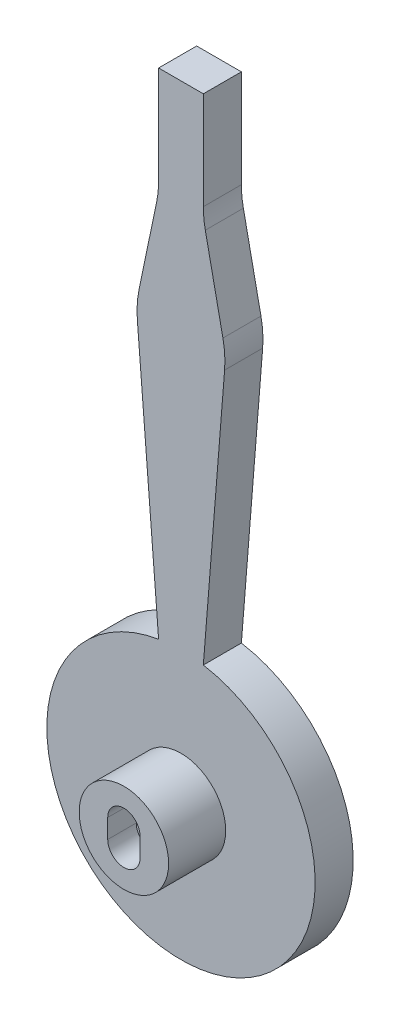
SolidWorks part; units mm, degrees
ref_plane "Front Plane" through (0, 0, 0) normal (0, 0, 1) x (1, 0, 0)
ref_plane "Top Plane" through (0, 0, 0) normal (0, 1, 0) x (1, 0, 0)
ref_plane "Right Plane" through (0, 0, 0) normal (1, 0, 0) x (0, 0, -1)
sketch "Sketch1" plane through (0, 0, 0) normal (0, 0, 1) x (1, 0, 0)
  line L0 (0, 0) -> (4.7, 0)
  line L1 (0, -14.1) -> (0, 65.9)
  line L2 (-4.7, 13.2936) -> (-4.7, 43.2936)
  line L3 (4.7, 13.2936) -> (4.7, 43.2936)
  line L4 (-4.4082, 44.6972) -> (-2.5594, 53.5898)
  line L5 (-2.35, 55.6253) -> (-2.35, 65.9)
  line L6 (-2.35, 65.9) -> (2.35, 65.9)
  line L7 (2.35, 65.9) -> (2.35, 55.6253)
  line L8 (2.5594, 53.5898) -> (4.4082, 44.6972)
  line L9 (-2.35, 13.9028) -> (-4.5857, 41.8646)
  line L10 (2.35, 13.9028) -> (4.5857, 41.8646)
  circle A0 centre (0, 0) radius 4.7
  circle A1 centre (0, 0) radius 14.1
  arc A2 (4.4082, 44.6972) -> (4.5857, 41.8646) centre (-5.3824, 42.6616) cw
  arc A3 (-4.4082, 44.6972) -> (-4.5857, 41.8646) centre (5.3824, 42.6616) ccw
  arc A4 (-2.35, 55.6253) -> (-2.5594, 53.5898) centre (-12.35, 55.6253) cw
  arc A5 (2.35, 55.6253) -> (2.5594, 53.5898) centre (12.35, 55.6253) ccw
  point P7 (-4.7, 0)
  point P8 (14.1, 0)
  point P9 (-14.1, 0)
  point P10 (4.7, 13.2936)
  point P11 (-4.7, 13.2936)
  point P16 (2.35, 54.5968)
  point P17 (-2.35, 54.5968)
  point P22 (-2.35, 13.9028)
  point P23 (2.35, 13.9028)
  point P34 (-2.35, 54.5968)
  point P37 (2.35, 54.5968)
  dimension "D3" = 28.2
  dimension "D8" = 10
  dimension "D9" = 10
  dimension "D10" = 10
  dimension "D11" = 10
  dimension "D1" = 4.7
  dimension "D2" = 80
  dimension "D4" = 30
  dimension "D5" = 30
  dimension "D6" = 13.2936
  dimension "D7" = 13.2936
  dimension "D12" = 4.7
  dimension "D13" = 27.9618
  dimension "D14" = 27.9618
  dimension "D15" = 10.2747
  dimension "D16" = 10.2747
  dimension "D17" = 23.49
extrude "Boss-Extrude1" add sketch "Sketch1" along normal blind 4 contours A1 L1 A0 | L1 A1 A0 | L5 A4 L4 A3 L9 A1 L1 L6 | A5 L7 L6 L1 A1 L10 A2 L8 region at (6.4829, 0, 0) region at (-6.4829, 0, 0) region at (-1.7258, 39.2066, 0) region at (1.7258, 39.2066, 0)
extrude "Boss-Extrude2" add sketch "Sketch1<3>" along normal blind 10 contours L1 A0 L0 | L0 A0 L1 | L1 A0 region at (1.9947, 1.9947, 0) region at (1.9947, -1.9947, 0) region at (-1.9947, 0, 0)
sketch "Sketch1<3>" plane through (0, 0, 0) normal (0, 0, 1) x (1, 0, 0) same geometry as "Sketch1"
sketch "Sketch2" plane through (0, 0, 10) normal (0, 0, 1) x (1, 0, 0)
  line L0 (0, 1) -> (0, -1) construction
  line L1 (1.7, 1) -> (1.7, -1)
  line L2 (-1.7, 1) -> (-1.7, -1)
  arc A0 (1.7, 1) -> (-1.7, 1) centre (0, 1) ccw
  arc A1 (-1.7, -1) -> (1.7, -1) centre (0, -1) ccw
  point P3 (0, 0)
  point P8 (0, 2.7)
  point P9 (0, -2.7)
  dimension "D1" = 5.4
  dimension "D2" = 3.4
extrude "Cut-Extrude1" cut sketch "Sketch2" against normal blind 3
